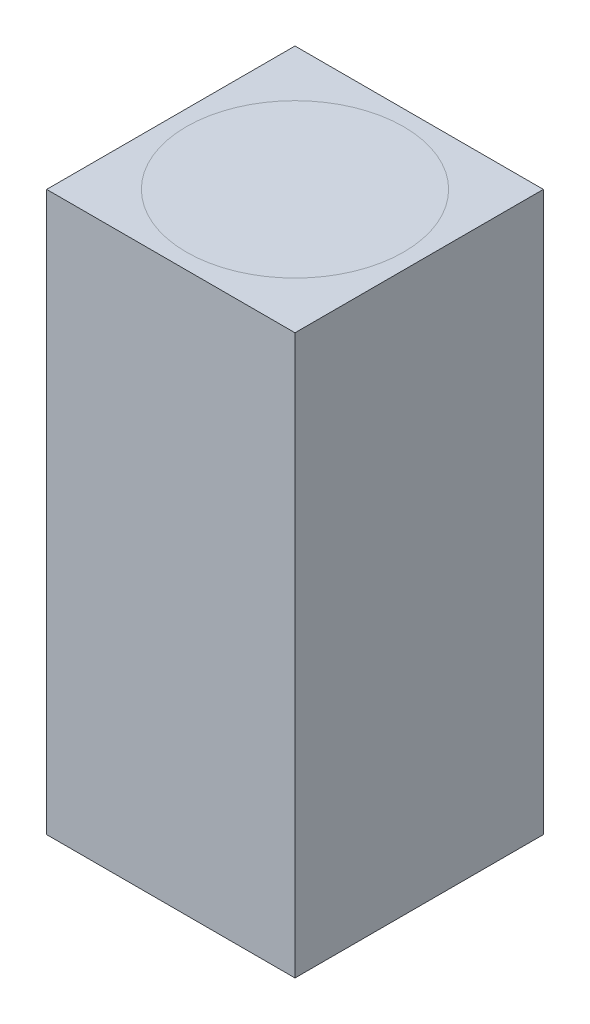
SolidWorks part; units mm, degrees
ref_plane "Front Plane" through (0, 0, 0) normal (0, 0, 1) x (1, 0, 0)
ref_plane "Top Plane" through (0, 0, 0) normal (0, 1, 0) x (1, 0, 0)
ref_plane "Right Plane" through (0, 0, 0) normal (1, 0, 0) x (0, 0, -1)
sketch "Sketch1" plane through (0, 0, 0) normal (0, 1, 0) x (1, 0, 0)
  line L1 (0, 0) -> (101.6, 0)
  line L2 (0, 0) -> (0, 101.6)
  line L3 (0, 101.6) -> (101.6, 101.6)
  line L4 (101.6, 0) -> (101.6, 101.6)
  circle A0 centre (50.8, 50.8) radius 44.45
  point P7 (101.6, 50.8)
  point P8 (44.45, 44.45)
  point P9 (50.8, 101.6)
  point P10 (0, 0)
  point P11 (44.45, 44.45)
  dimension "D3" = 88.9
  dimension "D1" = 101.6
  dimension "D2" = 101.6
extrude "Boss-Extrude1" add sketch "Sketch1" along normal blind 215.9
sketch "Sketch2" plane through (0, 0, 0) normal (0, -1, 0) x (1, 0, 0)
  line L4 (0, 0) -> (0, -101.6)
  line L5 (0, -101.6) -> (101.6, -101.6)
  line L6 (101.6, -101.6) -> (101.6, 0)
  line L7 (101.6, 0) -> (0, 0)
  line L8 (0, 0) -> (0, -101.6)
  line L9 (0, -101.6) -> (101.6, -101.6)
  line L10 (101.6, -101.6) -> (101.6, 0)
  line L11 (101.6, 0) -> (0, 0)
  dimension "D1" = 0
extrude "Boss-Extrude2" add sketch "Sketch2" along normal blind 6.35
sketch "Sketch4" plane through (0, 215.9, 0) normal (0, 1, 0) x (1, 0, 0)
  line L4 (0, 101.6) -> (0, 0)
  line L5 (0, 0) -> (101.6, 0)
  line L6 (101.6, 0) -> (101.6, 101.6)
  line L7 (101.6, 101.6) -> (0, 101.6)
  line L8 (0, 101.6) -> (0, 0)
  line L9 (0, 0) -> (101.6, 0)
  line L10 (101.6, 0) -> (101.6, 101.6)
  line L11 (101.6, 101.6) -> (0, 101.6)
  circle A0 centre (50.8, 50.8) radius 44.45 construction
  circle A1 centre (50.8, 50.8) radius 44.45
  dimension "D1" = 0
extrude "Boss-Extrude4" add sketch "Sketch4" along normal blind 6.35
sketch "Sketch5" plane through (0, 222.25, 0) normal (0, 1, 0) x (1, 0, 0)
  circle A0 centre (50.8, 50.8) radius 44.45 construction
  circle A1 centre (50.8, 50.8) radius 44.45
extrude "Boss-Extrude5" add sketch "Sketch5" against normal blind 6.35 separate body
